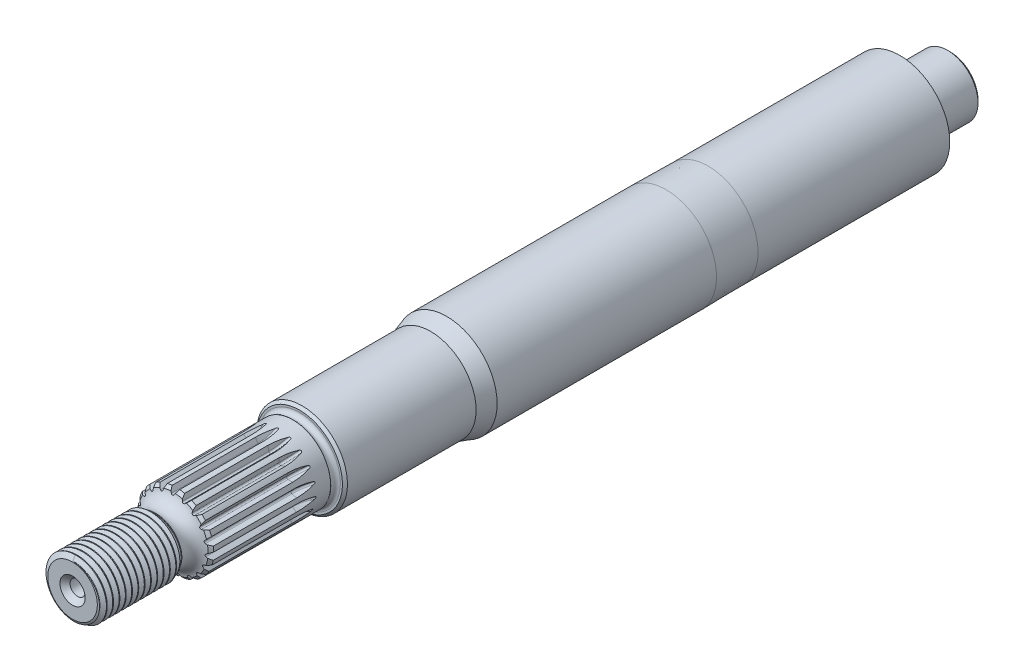
SolidWorks part; units mm, degrees
material "S355JR"
ref_plane "Front" through (0, 0, 0) normal (0, 0, 1) x (1, 0, 0)
ref_plane "Top" through (0, 0, 0) normal (0, 1, 0) x (1, 0, 0)
ref_plane "Right" through (0, 0, 0) normal (1, 0, 0) x (0, 0, -1)
sketch "Sketch1" plane through (0, 0, 0) normal (1, 0, 0) x (0, 0, -1)
  line L0 (0, 0) -> (2896.3878, 0) construction
  line L1 (-40, 0) -> (-40.9013, 1.5)
  line L2 (-40.9013, 1.5) -> (-44, 1.5)
  line L3 (-44, 1.5) -> (-45, 2.5)
  line L4 (-45, 2.5) -> (-45, 4.9175)
  line L5 (-45, 4.9175) -> (-44.4531, 5.8647)
  line L6 (-44.4531, 5.8647) -> (-29.5813, 5.8647)
  line L7 (-25, 7.5) -> (-1.3292, 7.5)
  line L8 (-45, 4.9175) -> (-45.625, 6) construction
  line L9 (-45.625, 6) -> (-44.375, 6) construction
  line L10 (-44.375, 6) -> (-45, 4.9175) construction
  line L11 (-45.625, 6) -> (-45.625, 5.7294) construction
  line L12 (-45.625, 5.7294) -> (-45.625, 5.4587) construction
  line L13 (-45.625, 5.4587) -> (-45.625, 5.1881) construction
  line L14 (-45.625, 5.1881) -> (-45.625, 4.9175) construction
  line L15 (-45.625, 4.9175) -> (-45, 4.9175) construction
  line L16 (-45.625, 5.8647) -> (-44.4531, 5.8647) construction
  line L17 (-45, 4.9175) -> (0, 4.9175) construction
  line L18 (0, 9) -> (0, 4.9175) construction
  line L19 (0, 9) -> (26, 9)
  line L20 (0, 9) -> (0, 8.1)
  line L21 (-0.8, 8.1) -> (-0.8, 7.3) construction
  line L22 (-0.8, 7.5) -> (-1.3292, 7.5) construction
  line L23 (26, 9) -> (29.1716, 10)
  line L24 (29.1716, 10) -> (72.6708, 10)
  line L26 (72.6708, 10) -> (81, 9.9)
  line L29 (81, 9.9) -> (119, 9.9)
  line L33 (119, 9.9) -> (119, 6.6)
  line L34 (120.3292, 6) -> (129, 6)
  line L35 (129, 6) -> (129, 2.5)
  line L36 (119.8, 6.6) -> (119.8, 5.8) construction
  line L37 (120.3292, 6) -> (119.8, 6) construction
  line L38 (129, 2.5) -> (128, 1.5)
  line L39 (128, 1.5) -> (124.9013, 1.5)
  line L40 (124.9013, 1.5) -> (124, 0)
  line L41 (124, 0) -> (-40, 0)
  arc A0 (-25, 7.5) -> (-29.5813, 5.8647) centre (-27.5825, 7.5) cw
  arc A1 (0, 8.1) -> (-1.3292, 7.5) centre (-0.8, 8.1) cw
  arc A7 (119, 6.6) -> (120.3292, 6) centre (119.8, 6.6) ccw
  dimension "D12" = 0.8
  dimension "D1" = 12
  dimension "D2" = 20
  dimension "D3" = 59
  dimension "D4" = 45
  dimension "D5" = 3
  dimension "D6" = 5
  dimension "D7" = 1.25
  dimension "D8" = 15
  dimension "D9" = 5
  dimension "D10" = 25
  dimension "D11" = 18
  dimension "D13" = 0.2
  dimension "D14" = 26
  dimension "D15" = 17.5
  dimension "D16" = 20
  dimension "D19" = 19.8
  dimension "D20" = 12
  dimension "D21" = 174
  dimension "D22" = 10
revolve "Revolve1" add sketch "Sketch1" angle 360 about L0
chamfer "Chamfer1" distance 0.5 angle 45 3 edges at (9, 0, 0) (6, 0, -129) (7.5, 0, 25)
sketch "Sketch2" plane through (0, 0, 45) normal (0, 0, 1) x (1, 0, 0)
  line L0 (-0.75, 7.4624) -> (-0.1681, 6.4978) construction
  line L1 (0.1681, 6.4978) -> (0.75, 7.4624) construction
  line L2 (-0.75, 7.4624) -> (-0.2569, 6.645)
  line L3 (0.2569, 6.645) -> (0.75, 7.4624)
  circle A0 centre (0, 0) radius 7.5 construction
  arc A1 (0.75, 7.4624) -> (-0.75, 7.4624) centre (0, 0) ccw
  arc A2 (0.1681, 6.4978) -> (-0.1681, 6.4978) centre (0, 0) ccw construction
  arc A3 (-0.2569, 6.645) -> (0.2569, 6.645) centre (0, 6.8) ccw
  point P4 (0, 6.5)
  point P5 (0, 7.5)
  dimension "D1" = 13
  dimension "D3" = 0.3
  dimension "D2" = 1.5
extrude "Cut-Extrude1" cut sketch "Sketch2" against normal blind 37
sketch "Sketch3" plane through (0, 0, 8) normal (0, 0, 1) x (1, 0, 0)
  line L0 (-3.98, 14.145) -> (5.0164, 14.145) construction
  line L2 (-0.75, 7.4624) -> (-0.2569, 6.645)
  line L3 (0.2569, 6.645) -> (0.75, 7.4624)
  line L4 (-0.75, 7.4624) -> (-0.2569, 6.645)
  line L5 (0.2569, 6.645) -> (0.75, 7.4624)
  arc A2 (0.75, 7.4624) -> (-0.75, 7.4624) centre (0, 0) ccw
  arc A3 (-0.2569, 6.645) -> (0.2569, 6.645) centre (0, 6.8) ccw
  arc A4 (0.75, 7.4624) -> (-0.75, 7.4624) centre (0, 0) ccw
  arc A5 (-0.2569, 6.645) -> (0.2569, 6.645) centre (0, 6.8) ccw
  dimension "D2" = 15
  dimension "D1" = 0
revolve "Cut-Revolve1" cut sketch "Sketch3" angle 360 about L0
pattern_circular "CirPattern1" count 19 over 360 about axis through (0, 0, 0) along (0, 0, 1) of "Cut-Revolve1", "Cut-Extrude1"
sketch "Sketch4" plane through (0, 0, 0) normal (1, 0, 0) x (0, 0, -1)
  line L0 (-45.5469, 5.8647) -> (-45.0781, 5.0528)
  line L1 (-45, 4.9175) -> (-45.625, 6) construction
  line L2 (-45.625, 5.8647) -> (-44.4531, 5.8647) construction
  line L3 (-44.9219, 5.0528) -> (-44.4531, 5.8647)
  line L4 (-44.4531, 5.8647) -> (-44.4531, 6)
  line L5 (-45.625, 6) -> (-44.375, 6) construction
  line L6 (-44.4531, 6) -> (-45.5469, 6)
  line L7 (-45.5469, 6) -> (-45.5469, 5.8647)
  line L8 (-45, 4.9175) -> (-44.4531, 5.8647) construction
  line L9 (-45.625, 5.0528) -> (-44.7152, 5.0528) construction
  line L10 (-45.625, 5.1881) -> (-45.625, 4.9175) construction
  arc A0 (-45.0781, 5.0528) -> (-44.9219, 5.0528) centre (-45, 5.0979) ccw
sketch "Sketch5" plane through (0, 0, 45) normal (0, 0, 1) x (1, 0, 0)
  circle A0 centre (0, 0) radius 5.8647 construction
  circle A1 centre (0, 0) radius 5.8647
curve "Helix/Spiral1" pitch 1.25 height 17 radius 5.8647 centre (0, 0, 45) axis (0, 0, -1) start towards (0, 1, 0)
sweep "Cut-Sweep1" cut profiles "Sketch4" path "Helix/Spiral1"
sketch "Sketch14" plane through (0, 0, -129) normal (0, 0, -1) x (-1, 0, 0)
  circle A4 centre (0, 0) radius 9.9 construction
  circle A5 centre (0, 0) radius 9.9
curve "Helix/Spiral2" pitch 460.5141 height 30 turns 0.0651
